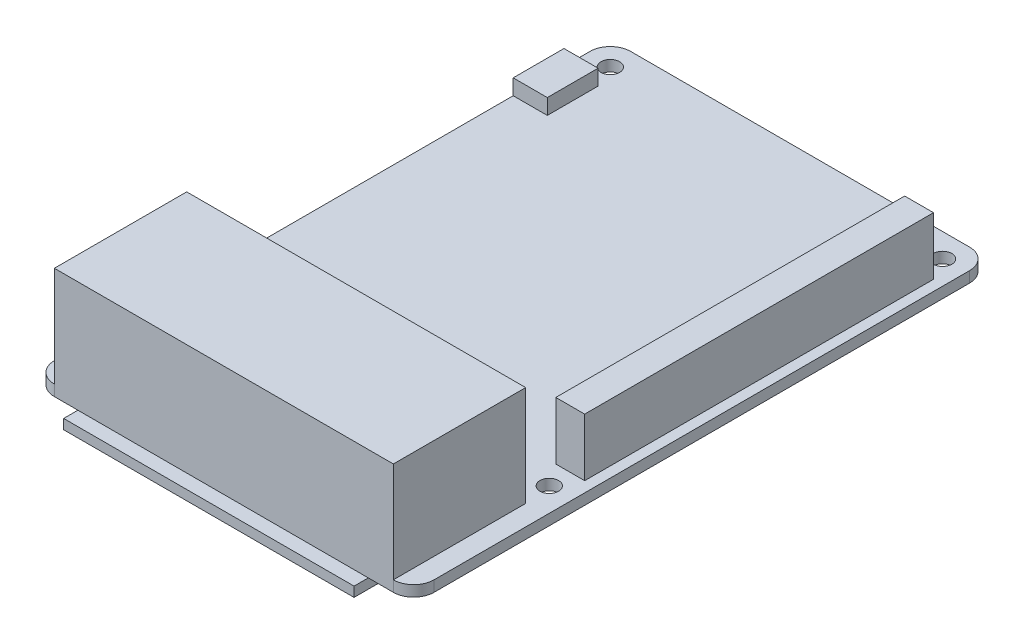
SolidWorks part; units mm, degrees
ref_plane "Front Plane" through (0, 0, 0) normal (0, 0, 1) x (1, 0, 0)
ref_plane "Top Plane" through (0, 0, 0) normal (0, 1, 0) x (1, 0, 0)
ref_plane "Right Plane" through (0, 0, 0) normal (1, 0, 0) x (0, 0, -1)
sketch "Sketch1" plane through (0, 0, 0) normal (0, 1, 0) x (1, 0, 0)
  line L1 (3, 0) -> (53, 0)
  line L2 (0, 3) -> (0, 82)
  line L3 (3, 85) -> (53, 85)
  line L4 (56, 3) -> (56, 82)
  arc A0 (0, 82) -> (3, 85) centre (3, 82) cw
  arc A1 (3, 0) -> (0, 3) centre (3, 3) cw
  arc A2 (53, 0) -> (56, 3) centre (53, 3) ccw
  arc A3 (53, 85) -> (56, 82) centre (53, 82) cw
  point P7 (0, 85)
  point P10 (0, 0)
  point P15 (56, 85)
  dimension "D3" = 3
  dimension "D1" = 85
  dimension "D2" = 56
extrude "Boss-Extrude1" add sketch "Sketch1" along normal blind 1.6002
hole_wizard "Ø2.7 (2.7) Diameter Hole1" positions "Sketch2" profile "Sketch3" hole size "Ø2.7" standard "ANSI Metric" end condition through all
sketch "Sketch2" plane through (0, 1.6002, 0) normal (0, 1, 0) x (1, 0, 0)
  line L0 (53, 85) -> (3, 85) construction
  line L1 (0, 82) -> (0, 3) construction
  point P0 (3.5, 81.5)
  point P2 (3.5, 23.5)
  point P9 (52.5, 81.5)
  point P11 (52.5, 23.5)
  dimension "D1" = 3.5
  dimension "D2" = 3.5
  dimension "D3" = 58
  dimension "D4" = 49
sketch "Sketch3" plane through (3.5, 1.6002, -81.5) normal (1, 0, 0) x (0, 0, 1)
  line L0 (0, 0) -> (0, 1.6002)
  line L1 (0, 1.6002) -> (1.375, 1.6002)
  line L2 (1.375, 1.6002) -> (1.375, 0)
  line L5 (1.375, 0) -> (0, 0)
  line L11 (0, -6.35) -> (0, 107.95) construction
  dimension "Thru Hole Dia." = 2.75
  dimension "Thru Hole Depth" = 1.6002
sketch "Sketch4" plane through (0, 1.6002, 0) normal (0, 1, 0) x (1, 0, 0)
  line L0 (3, 0) -> (53, 0) construction
  line L1 (3, 0) -> (53, 0)
  line L2 (3, 0) -> (3, 19.5171)
  line L3 (3, 19.5171) -> (53, 19.5171)
  line L4 (53, 0) -> (53, 19.5171)
extrude "Boss-Extrude2" add sketch "Sketch4" along normal blind 14.8
sketch "Sketch5" plane through (0, 0, 0) normal (0, -1, 0) x (1, 0, 0)
  line L0 (53, -85) -> (3, -85) construction
  line L2 (6.4683, -80.1436) -> (49.3033, -80.1436)
  line L3 (6.4683, -80.1436) -> (6.4683, 2.1)
  line L4 (6.4683, 2.1) -> (49.3033, 2.1)
  line L5 (49.3033, -80.1436) -> (49.3033, 2.1)
  dimension "D1" = 87.1
extrude "Boss-Extrude3" add sketch "Sketch5" along normal blind 1.4478
sketch "Sketch6" plane through (0, 1.6002, 0) normal (0, 1, 0) x (1, 0, 0)
  line L0 (0, 82) -> (0, 3) construction
  line L1 (0, 78.1674) -> (5.0329, 78.1674)
  line L2 (0, 78.1674) -> (0, 70.6744)
  line L3 (0, 70.6744) -> (5.0329, 70.6744)
  line L4 (5.0329, 78.1674) -> (5.0329, 70.6744)
  line L5 (53, 85) -> (3, 85) construction
  dimension "D1" = 6.8326
  dimension "D2" = 7.493
extrude "Boss-Extrude4" add sketch "Sketch6" along normal blind 2.286 separate body
sketch "Sketch7" plane through (0, 1.6002, 0) normal (0, 1, 0) x (1, 0, 0)
  line L1 (54.448, 26.7706) -> (50.1913, 26.7706)
  line L2 (54.448, 26.7706) -> (54.448, 78.2268)
  line L3 (54.448, 78.2268) -> (50.1913, 78.2268)
  line L4 (50.1913, 26.7706) -> (50.1913, 78.2268)
extrude "Boss-Extrude5" add sketch "Sketch7" along normal blind 8.509
